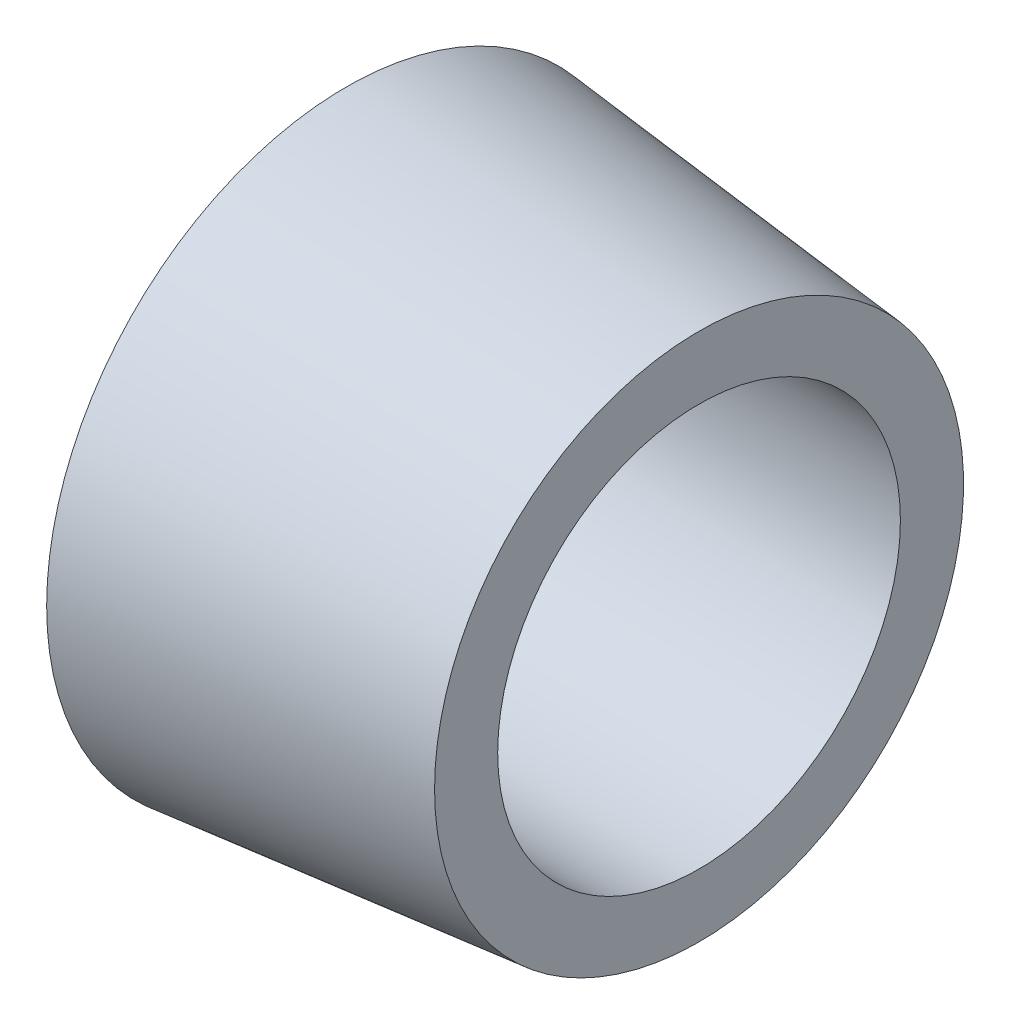
SolidWorks part; units mm, degrees
ref_plane "Front Plane" through (0, 0, 0) normal (0, 0, 1) x (1, 0, 0)
ref_plane "Top Plane" through (0, 0, 0) normal (0, 1, 0) x (1, 0, 0)
ref_plane "Right Plane" through (0, 0, 0) normal (1, 0, 0) x (0, 0, -1)
sketch "Sketch1" plane through (0, 0, 0) normal (0, 0, 1) x (1, 0, 0)
  line L0 (0, 14.5034) -> (25.4, 14.5034)
  line L1 (0, 14.5034) -> (0, 21.59)
  line L2 (0, 21.59) -> (25.4, 19.05)
  line L3 (25.4, 19.05) -> (25.4, 14.5034)
  point P0 (0.8337, 21.59)
  point P5 (0, 0)
  point P7 (0, 0)
  point P8 (-0.2288, 1.531)
  point P9 (-0.2288, 1.2699)
  dimension "D1" = 25.4
  dimension "D2" = 4.5466
  dimension "D3" = 7.0866
  dimension "D4" = 14.5034
ref_axis "Axis1" through (-1.27, 0, 0) along (1, 0, 0)
revolve "Revolve1" add sketch "Sketch1" angle 360 about axis through (-1.27, 0, 0) along (1, 0, 0)
